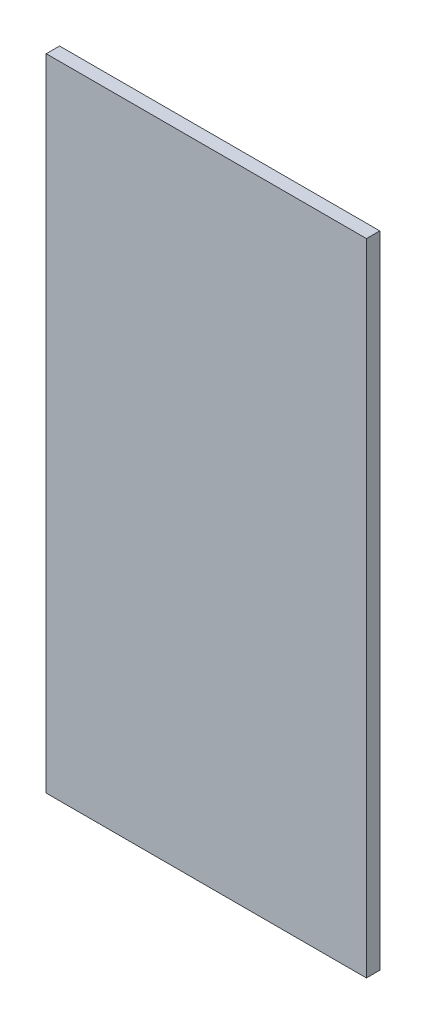
SolidWorks part; units mm, degrees
material "6061 Alloy"
ref_plane "Front Plane" through (0, 0, 0) normal (0, 0, 1) x (1, 0, 0)
ref_plane "Top Plane" through (0, 0, 0) normal (0, 1, 0) x (1, 0, 0)
ref_plane "Right Plane" through (0, 0, 0) normal (1, 0, 0) x (0, 0, -1)
sketch "Sketch1" plane through (0, 0, 0) normal (0, 0, 1) x (1, 0, 0)
  line L1 (-76.2, 152.4) -> (76.2, 152.4)
  line L2 (-76.2, 152.4) -> (-76.2, -152.4)
  line L3 (-76.2, -152.4) -> (76.2, -152.4)
  line L4 (76.2, 152.4) -> (76.2, -152.4)
  line L5 (-76.2, 152.4) -> (76.2, -152.4) construction
  line L6 (-76.2, -152.4) -> (76.2, 152.4) construction
  point P0 (0, 0)
  dimension "D1" = 304.8
  dimension "D2" = 152.4
extrude "Boss-Extrude1" add sketch "Sketch1" along normal blind 6.35
